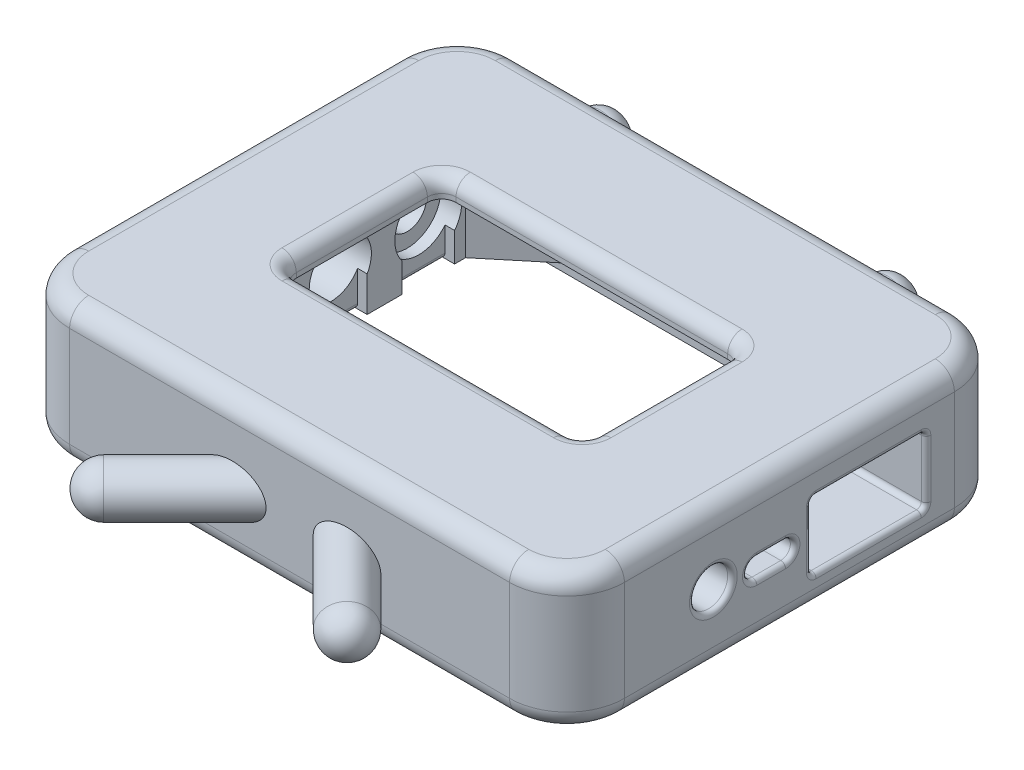
SolidWorks part; units mm, degrees
ref_plane "前视基准面" through (0, 0, 0) normal (0, 0, 1) x (1, 0, 0)
ref_plane "上视基准面" through (0, 0, 0) normal (0, 1, 0) x (1, 0, 0)
ref_plane "右视基准面" through (0, 0, 0) normal (1, 0, 0) x (0, 0, -1)
sketch "草图1" plane through (0, 0, 0) normal (0, 1, 0) x (1, 0, 0)
  line L0 (0, -23.25) -> (0, 24.5) construction
  line L7 (-29, 23.25) -> (29, 23.25)
  line L8 (-29, 23.25) -> (-29, -23.25)
  line L9 (-29, -23.25) -> (29, -23.25)
  line L10 (29, 23.25) -> (29, -23.25)
  line L11 (-29, 23.25) -> (29, -23.25) construction
  line L12 (-29, -23.25) -> (29, 23.25) construction
  line L13 (-29, 23.25) -> (29, 23.25) construction
  line L20 (-19.2, -17.25) -> (19.2, -17.25)
  line L21 (-19.2, -17.25) -> (-19.2, 20.15)
  line L22 (-19.2, 20.15) -> (19.2, 20.15)
  line L23 (19.2, -17.25) -> (19.2, 20.15)
  line L24 (-19.2, -17.25) -> (19.2, 20.15) construction
  line L25 (-19.2, 20.15) -> (19.2, -17.25) construction
  point P0 (0, 0)
  point P3 (0, 1.45)
  point P6 (0, 0)
  dimension "D1" = 58
  dimension "D2" = 46.5
  dimension "D3" = 6
  dimension "D4" = 38.4
  dimension "D5" = 37.4
  dimension "D6" = 3.1
extrude "凸台-拉伸1" add sketch "草图1" along normal blind 12.5
sketch "草图2" plane through (0, 12.5, 0) normal (0, 1, 0) x (1, 0, 0)
  line L13 (15.7, -8.35) -> (-15.7, -8.35)
  line L18 (15.7, -8.35) -> (15.7, 8.35)
  line L19 (15.7, 8.35) -> (-15.7, 8.35)
  line L20 (-15.7, -8.35) -> (-15.7, 8.35)
  line L25 (15.7, -8.35) -> (-15.7, 8.35) construction
  line L39 (15.7, 8.35) -> (-15.7, -8.35) construction
  line L40 (29, -23.25) -> (-29, -23.25)
  line L41 (29, -23.25) -> (29, 23.25)
  line L42 (29, 23.25) -> (-29, 23.25)
  line L43 (-29, -23.25) -> (-29, 23.25)
  line L44 (29, -23.25) -> (-29, 23.25) construction
  line L45 (29, 23.25) -> (-29, -23.25) construction
  point P0 (0, 0)
  point P4 (0, 0)
  dimension "D1" = 31.4
  dimension "D2" = 16.7
extrude "凸台-拉伸2" add sketch "草图2" along normal blind 2
fillet "圆角1" radius 6 4 edges at (29, 7.25, 23.25) (29, 7.25, -23.25) (-29, 7.25, -23.25) (-29, 7.25, 23.25)
sketch "草图11" plane through (0, 0, 23.25) normal (0, 0, 1) x (1, 0, 0)
  line L0 (0, 14.5) -> (0, 0)
  line L2 (-6, 13) -> (-6, 0) construction
  line L3 (-23, 0) -> (23, 0) construction
  line L4 (6, 13) -> (6, 0) construction
  line L6 (-23, 14.5) -> (23, 14.5) construction
  dimension "D1" = 6
  dimension "D2" = 6
ref_plane "left" through (14.625, 0, 14.625) normal (0.7071, 0, 0.7071) x (0, -1, 0)
ref_plane "right" through (-14.625, 0, 14.625) normal (-0.7071, 0, 0.7071) x (0, -1, 0)
sketch "草图8" plane through (-14.625, 0, 14.625) normal (-0.7071, 0, 0.7071) x (0, -1, 0)
  line L0 (-13, 12.1976) -> (0, 12.1976) construction
  circle A0 centre (-6.5, 12.1976) radius 2.5
  dimension "D1" = 5
extrude "凸台-拉伸3" add sketch "草图8" along normal blind 12 and the other way blind 3
sketch "草图9" plane through (14.625, 0, 14.625) normal (0.7071, 0, 0.7071) x (0, -1, 0)
  line L0 (-13, -12.1976) -> (0, -12.1976) construction
  circle A0 centre (-6.5, -12.1976) radius 2.5
  dimension "D1" = 5
extrude "凸台-拉伸4" add sketch "草图9" along normal blind 12 and the other way blind 3
fillet "圆角8" radius 2.5 2 edges at (-12.7175, 6.5, 33.503) (16.253, 6.5, 29.9675)
fillet "圆角10" radius 2 8 edges at (-27.2426, 0, -21.4926) (27.2426, 0, -21.4926) (29, 0, 0) (27.2426, 0, 21.4926) (-27.2426, 0, 21.4926) (-29, 0, 0) (0, 0, 23.25) (0, 0, -23.25)
fillet "圆角11" radius 1.5 8 edges at (15.7, 14.5, 0) (0, 14.5, -8.35) (-15.7, 14.5, 0) (0, 14.5, 8.35) (-15.7, 13.5, 8.35) (15.7, 13.5, 8.35) (15.7, 13.5, -8.35) (-15.7, 13.5, -8.35)
fillet "圆角12" radius 2 8 edges at (27.2426, 14.5, 21.4926) (0, 14.5, 23.25) (-27.2426, 14.5, 21.4926) (-29, 14.5, 0) (-27.2426, 14.5, -21.4926) (0, 14.5, -23.25) (27.2426, 14.5, -21.4926) (29, 14.5, 0)
sketch "草图12" plane through (0, 0, 0) normal (0, -1, 0) x (1, 0, 0)
  line L0 (-19.2, 17.25) -> (19.2, 17.25) construction
  line L1 (-25, 17.25) -> (25, 17.25)
  line L2 (-25, 17.25) -> (-25, -20.15)
  line L3 (-25, -20.15) -> (25, -20.15)
  line L4 (25, 17.25) -> (25, -20.15)
  line L5 (19.2, -20.15) -> (-19.2, -20.15) construction
  point P9 (0, 17.25)
  dimension "D1" = 50
  dimension "D2" = 37.4
extrude "切除-拉伸1" cut sketch "草图12" against normal blind 2
fillet "圆角13" radius 5 4 edges at (25, 1, 17.25) (25, 1, -20.15) (-25, 1, -20.15) (-25, 1, 17.25)
sketch "草图14" plane through (0, 12.5, 0) normal (0, -1, 0) x (1, 0, 0)
  line L0 (0, -20.15) -> (0, 17.25) construction
  line L1 (19.2, -20.15) -> (-19.2, -20.15) construction
  line L2 (-19.2, 17.25) -> (19.2, 17.25) construction
  line L3 (19.2, -1.45) -> (-19.2, -1.45) construction
  line L4 (19.2, 17.25) -> (19.2, -20.15) construction
  line L5 (-19.2, -20.15) -> (-19.2, 17.25) construction
  line L6 (-12.2, 17.25) -> (-19.2, 11.45)
  line L7 (-19.2, 11.45) -> (-19.2, 17.25)
  line L8 (-19.2, 17.25) -> (-12.2, 17.25)
  line L9 (19.2, 17.25) -> (12.2, 17.25)
  line L10 (19.2, 11.45) -> (19.2, 17.25)
  line L11 (12.2, 17.25) -> (19.2, 11.45)
  line L12 (12.2, -20.15) -> (19.2, -14.35)
  line L13 (19.2, -14.35) -> (19.2, -20.15)
  line L14 (19.2, -20.15) -> (12.2, -20.15)
  line L15 (-19.2, -20.15) -> (-12.2, -20.15)
  line L16 (-19.2, -14.35) -> (-19.2, -20.15)
  line L17 (-12.2, -20.15) -> (-19.2, -14.35)
  dimension "D1" = 5.8
  dimension "D2" = 7
extrude "凸台-拉伸5" add sketch "草图14" along normal up to surface (10.5 mm away) up to face at (-21.7452, 2, -1.45)
sketch "草图16" plane through (-29, 0, 0) normal (-1, 0, 0) x (0, 0, 1)
  line L1 (17.25, 12.5) -> (-17.25, 12.5) construction
  line L3 (-17.25, 12.5) -> (-17.25, 2) construction
  circle A0 centre (-1.25, 7.32) radius 3.25
  dimension "D1" = 6.5
  dimension "D2" = 5.18
  dimension "D3" = 16
extrude "切除-拉伸3" cut sketch "草图16" against normal up to next
sketch "草图17" plane through (-29, 0, 0) normal (-1, 0, 0) x (0, 0, 1)
  line L0 (-1.25, 10.57) -> (-1.25, 4.07) construction
  line L1 (17.25, 12.5) -> (-17.25, 12.5) construction
  line L2 (17.25, 2) -> (17.25, 12.5) construction
  circle A0 centre (-1.25, 7.32) radius 3.25 construction
  circle A1 centre (7.95, 7.21) radius 2
  circle A2 centre (-10.45, 7.21) radius 2
  point P9 (-1.25, 7.32)
  dimension "D1" = 4
  dimension "D2" = 5.29
  dimension "D3" = 9.2
  dimension "D4" = 9.3
extrude "切除-拉伸4" cut sketch "草图17" against normal up to next
sketch "草图18" plane through (29, 0, 0) normal (1, 0, 0) x (0, 0, -1)
  line L0 (-17.25, 12.5) -> (-17.25, 2) construction
  line L1 (17.25, 12.5) -> (-17.25, 12.5) construction
  circle A0 centre (-7.95, 7.21) radius 2
  dimension "D1" = 4
  dimension "D2" = 9.3
  dimension "D3" = 5.29
extrude "切除-拉伸5" cut sketch "草图18" against normal up to next
sketch "草图19" plane through (29, 0, 0) normal (1, 0, 0) x (0, 0, -1)
  line L0 (-3.4, 6.81) -> (-0.4, 6.81) construction
  line L1 (-3.4, 7.81) -> (-0.4, 7.81)
  line L2 (-3.4, 5.81) -> (-0.4, 5.81)
  line L3 (17.25, 12.5) -> (-17.25, 12.5) construction
  line L4 (-17.25, 12.5) -> (-17.25, 2) construction
  arc A0 (-3.4, 7.81) -> (-3.4, 5.81) centre (-3.4, 6.81) ccw
  arc A1 (-0.4, 5.81) -> (-0.4, 7.81) centre (-0.4, 6.81) ccw
  point P2 (-1.9, 6.81)
  dimension "D4" = 3
  dimension "D1" = 2
  dimension "D2" = 5.69
  dimension "D3" = 15.35
extrude "切除-拉伸6" cut sketch "草图19" against normal up to next
sketch "草图20" plane through (29, 0, 0) normal (1, 0, 0) x (0, 0, -1)
  line L0 (-17.25, 12.5) -> (-17.25, 2) construction
  line L1 (2.29, 10.31) -> (14.29, 10.31)
  line L2 (2.29, 10.31) -> (2.29, 3.31)
  line L3 (2.29, 3.31) -> (14.29, 3.31)
  line L4 (14.29, 10.31) -> (14.29, 3.31)
  line L5 (2.29, 10.31) -> (14.29, 3.31) construction
  line L6 (2.29, 3.31) -> (14.29, 10.31) construction
  line L7 (17.25, 12.5) -> (-17.25, 12.5) construction
  point P0 (8.29, 6.81)
  dimension "D1" = 12
  dimension "D2" = 7
  dimension "D3" = 25.54
  dimension "D4" = 5.69
extrude "切除-拉伸7" cut sketch "草图20" against normal up to next
fillet "圆角14" radius 0.5 12 edges at (29, 6.81, 4.4) (29, 7.81, 1.9) (29, 6.81, -0.6) (-29, 7.21, -12.45) (-29, 7.21, 9.95) (-29, 7.32, 2) (29, 5.81, 1.9) (29, 7.21, 5.95) (24.1, 10.31, -14.29) (24.1, 3.31, -14.29) (24.1, 3.31, -2.29) (24.1, 10.31, -2.29)
fillet "圆角15" radius 0.5 8 edges at (29, 3.4564, -2.4364) (29, 6.81, -2.29) (29, 10.1636, -2.4364) (29, 10.31, -8.29) (29, 10.1636, -14.1436) (29, 6.81, -14.29) (29, 3.4564, -14.1436) (29, 3.31, -8.29)
sketch "草图21" plane through (19.2, 0, 0) normal (-1, 0, 0) x (0, 0, 1)
  circle A0 centre (7.95, 7.21) radius 3.5
  dimension "D1" = 7
extrude "切除-拉伸8" cut sketch "草图21" against normal blind 2.2
sketch "草图22" plane through (-19.2, 0, 0) normal (1, 0, 0) x (0, 0, -1)
  circle A0 centre (-7.95, 7.21) radius 3.5
  circle A1 centre (10.45, 7.21) radius 3.5
  dimension "D1" = 7
  dimension "D2" = 7
extrude "切除-拉伸9" cut sketch "草图22" against normal blind 2.2
sketch "草图23" plane through (-19.2, 0, 0) normal (1, 0, 0) x (0, 0, -1)
  line L0 (-11.45, 2) -> (14.35, 2) construction
  line L1 (-10.7, 12.42) -> (-5.2, 12.42) construction
  line L2 (-10.7, 12.42) -> (-10.7, 2) construction
  line L3 (-10.7, 2) -> (-5.2, 2)
  line L4 (-5.2, 12.42) -> (-5.2, 2) construction
  line L5 (-10.7, 12.42) -> (-5.2, 2) construction
  line L6 (-10.7, 2) -> (-5.2, 12.42) construction
  line L7 (-10.7, 2) -> (-10.7, 7.21)
  line L8 (-1.4419, 12.42) -> (4.0581, 12.42) construction
  line L9 (-1.4419, 12.42) -> (-1.4419, 2) construction
  line L10 (-1.4419, 2) -> (4.0581, 2)
  line L11 (4.0581, 12.42) -> (4.0581, 2) construction
  line L12 (-1.4419, 12.42) -> (4.0581, 2) construction
  line L13 (-1.4419, 2) -> (4.0581, 12.42) construction
  line L14 (7.7, 12.42) -> (13.2, 12.42) construction
  line L15 (7.7, 12.42) -> (7.7, 2) construction
  line L16 (7.7, 2) -> (13.2, 2)
  line L17 (13.2, 12.42) -> (13.2, 2) construction
  line L18 (7.7, 12.42) -> (13.2, 2) construction
  line L19 (7.7, 2) -> (13.2, 12.42) construction
  line L20 (-10.7, 7.21) -> (-5.2, 7.21)
  line L21 (-5.2, 7.21) -> (-5.2, 2)
  line L22 (-1.4419, 2) -> (-1.4419, 7.21)
  line L23 (-1.4419, 7.21) -> (4.0581, 7.21)
  line L24 (4.0581, 7.21) -> (4.0581, 2)
  line L25 (7.7, 2) -> (7.7, 7.21)
  line L26 (7.7, 7.21) -> (13.2, 7.21)
  line L27 (13.2, 7.21) -> (13.2, 2)
  point P0 (-7.95, 7.21)
  point P8 (1.25, 7.32)
  point P14 (10.45, 7.21)
  dimension "D1" = 5.5
extrude "切除-拉伸10" cut sketch "草图23" against normal blind 1
fillet "圆角16" radius 0.5 3 edges at (-20.2, 2, -10.45) (-20.2, 2, -1.3081) (-20.2, 2, 7.95)
sketch "草图24" plane through (0, 0, -23.25) normal (0, 0, -1) x (-1, 0, 0)
  line L0 (0, 12.5) -> (0, 2) construction
  line L1 (23, 12.5) -> (-23, 12.5) construction
  line L2 (-23, 2) -> (23, 2) construction
  line L3 (12.5, 10) -> (12.5, 0)
  line L10 (23, 0) -> (27, 0) construction
  line L23 (-17.5, 10) -> (-17.5, 0)
  line L24 (-17.5, 0) -> (-12.5, 0)
  line L25 (-12.5, 10) -> (-12.5, 0)
  line L26 (17.5, 0) -> (12.5, 0)
  line L33 (17.5, 10) -> (17.5, 0)
  arc A4 (12.5, 10) -> (17.5, 10) centre (15, 10) cw
  arc A5 (-12.5, 10) -> (-17.5, 10) centre (-15, 10) ccw
  point P10 (0, 0)
  point P17 (15, 12.5)
  point P20 (-15, 12.5)
  dimension "D1" = 15
  dimension "D2" = 5
extrude "凸台-拉伸6" add sketch "草图24" along normal blind 3 and the other way up to next
sketch "草图26" plane through (0, 2, 0) normal (0, -1, 0) x (1, 0, 0)
  line L0 (-25, -1.45) -> (25, -1.45) construction
  line L1 (-25, 12.25) -> (-25, -15.15) construction
  line L2 (25, -15.15) -> (25, 12.25) construction
  line L3 (0, -1.45) -> (0, -20.5649) construction
  circle A0 centre (-20, 14.55) radius 1.05
  circle A1 centre (20, 14.55) radius 1.05
  circle A2 centre (20, -17.45) radius 1.05
  circle A3 centre (-20, -17.45) radius 1.05
  point P6 (0, -1.45)
  dimension "D1" = 2.1
  dimension "D2" = 20
  dimension "D3" = 16
extrude "切除-拉伸11" cut sketch "草图26" against normal blind 8
fillet "圆角19" radius 0.5 4 edges at (-20, 2, -16.4) (-20, 2, 13.5) (20, 2, -18.5) (20, 2, 15.6)
fillet "圆角20" radius 2 12 edges at (12.5, 5, -26.25) (15, 12.5, -26.25) (17.5, 5, -26.25) (15, 0, -26.25) (-17.5, 5, -26.25) (-12.5, 5, -26.25) (17.5, 0, -23.75) (12.5, 0, -23.75) (-17.5, 0, -23.75) (-12.5, 0, -23.75) (-15, 0, -26.25) (-15, 12.5, -26.25)
